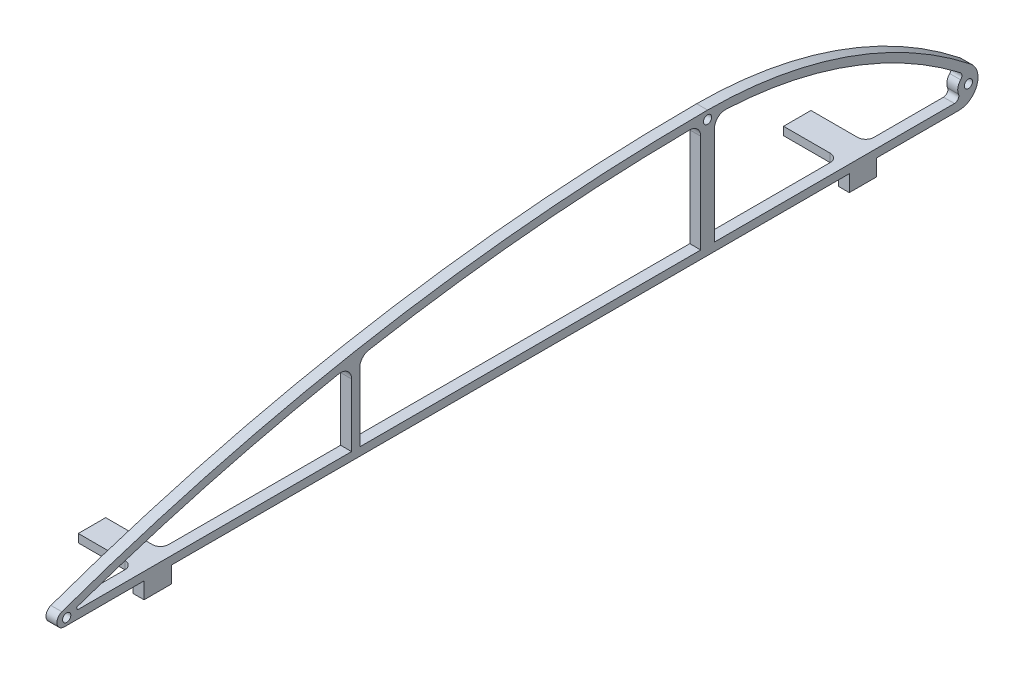
SolidWorks part; units mm, degrees
other "Marquage1"
sketch "Esquisse8" plane through (8, 0, -172.8424) normal (1, 0, 0) x (0, 0, -1)
other "Marquage2"
sketch "Esquisse10" plane through (-6, 20, -172.8424) normal (-0.8365, 0.2588, -0.483) x (-0.5, 0, 0.866)
other "Marquage3"
sketch "Esquisse11" plane through (0, 0, 0) normal (-0.0501, -0.1345, 0.9896) x (0.9942, 0.0873, 0.0622)
ref_plane "Plan de face" through (0, 0, 0) normal (0, 0, 1) x (1, 0, 0)
ref_plane "Plan de dessus" through (0, 0, 0) normal (0, 1, 0) x (1, 0, 0)
ref_plane "Plan de droite" through (0, 0, 0) normal (1, 0, 0) x (0, 0, -1)
sketch "Esquisse2" plane through (0, 0, 0) normal (1, 0, 0) x (0, 0, -1)
  line L0 (0, 0) -> (170.8732, 0)
  arc A1 (173.0499, 6.2408) -> (125, 23) centre (125, -54.2609) ccw
  arc A3 (170.8732, 0) -> (173.0499, 6.2408) centre (170.8732, 3.5) ccw
  arc A4 (125, 23) -> (0, 0) centre (125, -328.1739) ccw
  point P10 (180, 0)
  dimension "D1" = 180
  dimension "D2" = 3.5
  dimension "D3" = 23
  dimension "D4" = 55
extrude "Boss.-Extru.1" add sketch "Esquisse2" along normal blind 2
sketch "Esquisse4" plane through (2, 0, 0) normal (1, 0, 0) x (0, 0, -1)
  line L1 (0, 0) -> (8, 1.25) construction
  line L10 (174.369, 3.3283) -> (172.619, 3.3283) construction
  circle A6 centre (125, 21.5) radius 0.75
  circle A12 centre (172.619, 3.3283) radius 0.75
  arc A13 (170.8732, 0) -> (173.0499, 6.2408) centre (170.8732, 3.5) ccw construction
  circle A15 centre (8, 1.25) radius 0.75
  dimension "D1" = 1.5
  dimension "D2" = 1.5
  dimension "D7" = 1.5
  dimension "D3" = 1.5
  dimension "D4" = 8
  dimension "D5" = 1.25
  dimension "D6" = 1.75
extrude "Enlèv. mat.-Extru.2" cut sketch "Esquisse4" against normal through all
sketch "Esquisse9" plane through (0, 0, 0) normal (1, 0, 0) x (0, 0, -1)
  line L26 (126.25, 1.5) -> (171.941, 1.5)
  line L35 (8.4369, 1.5) -> (170.8732, 1.5)
  line L36 (9.9339, 1.5) -> (60, 1.5)
  line L40 (61.5, 1.5) -> (123.75, 1.5)
  line L42 (60, 1.5) -> (60, 15.4055)
  line L44 (61.5, 1.5) -> (61.5, 15.6859)
  line L45 (123.75, 21.4978) -> (123.75, 1.5)
  line L46 (126.25, 21.4978) -> (126.25, 1.5)
  arc A20 (60, 15.4055) -> (9.8076, 1.9814) centre (125, -328.1739) ccw
  circle A21 centre (125, 21.5) radius 0.75 construction
  circle A22 centre (8, 1.25) radius 0.75 construction
  arc A23 (173.0499, 6.2408) -> (125, 23) centre (125, -54.2609) ccw construction
  arc A25 (171.9926, 5.175) -> (171.941, 1.5) centre (172.619, 3.3283) ccw
  circle A26 centre (172.619, 3.3283) radius 0.75 construction
  arc A35 (170.8732, 1.5) -> (172.117, 5.0662) centre (170.8732, 3.5) ccw
  arc A39 (172.117, 5.0662) -> (125, 21.5) centre (125, -54.2609) ccw
  arc A40 (125, 21.5) -> (8.4369, 1.5) centre (125, -328.1739) ccw
  arc A42 (171.9926, 5.175) -> (126.25, 21.4978) centre (125, -54.2609) ccw
  arc A43 (123.75, 21.4978) -> (61.5, 15.6859) centre (125, -328.1739) ccw
  arc A54 (9.9339, 1.5) -> (9.8076, 1.9814) centre (8, 1.25) ccw
  dimension "D1" = 1.5
  dimension "D2" = 1.25
  dimension "D3" = 1.2
  dimension "D5" = 1.25
  dimension "D4" = 1.2
  dimension "D6" = 1.5
  dimension "D7" = 60
extrude "Enlèv. mat.-Extru.3" cut sketch "Esquisse9" along normal blind 4
fillet "Congé2" radius 1.35 1 edges at (1, 0, 0)
sketch "Esquisse12" plane through (0, 0, 0) normal (0, -1, 0) x (1, 0, 0)
  line L0 (0, -155.8732) -> (2, -155.8732)
  line L1 (0, -7.5659) -> (0, -170.8732) construction
  line L2 (2, -7.5659) -> (2, -170.8732) construction
  line L3 (2, -170.8732) -> (0, -170.8732) construction
  line L4 (0, -150.8732) -> (2, -150.8732)
  line L5 (0, -27.1127) -> (2, -27.1127)
  line L6 (0, -22.1127) -> (2, -22.1127)
  line L7 (0, -7.1127) -> (2, -7.1127) construction
  line M5 (2, -170.8732) -> (2, -7.5659)
  line M7 (0, -7.5659) -> (0, -170.8732)
  dimension "D1" = 15
  dimension "D2" = 5
  dimension "D3" = 15
  dimension "D4" = 5
extrude "Boss.-Extru.2" add sketch "Esquisse12" along normal blind 3 contours L4 L0 M7 M5 | L6 L5 M7 M5 region at (1, 0, -153.3732) region at (1, 0, -24.6127)
fillet "Congé3" radius 2 4 edges at (1, 21.4978, -126.25) (1, 21.4978, -123.75) (1, 15.4055, -60) (1, 15.6859, -61.5)
fillet "Congé4" radius 0.8 2 edges at (1, 1.5, -171.941) (1, 5.175, -171.9926)
sketch "Esquisse13" plane through (0, 0, 0) normal (-1, 0, 0) x (0, 0, 1)
  line L1 (-150.8732, -3) -> (-150.8732, 0) construction
  line L2 (-155.8732, 0) -> (-150.8732, 0)
  line L3 (-155.8732, 0) -> (-155.8732, 1.5)
  line L4 (-155.8732, 1.5) -> (-150.8732, 1.5)
  line L5 (-150.8732, 0) -> (-150.8732, 1.5)
  line L6 (-126.25, 1.5) -> (-170.0685, 1.5) construction
  line L7 (-22.1127, -3) -> (-22.1127, 0) construction
  line L8 (-27.1127, 0) -> (-22.1127, 0)
  line L9 (-27.1127, 0) -> (-27.1127, 1.5)
  line L10 (-27.1127, 1.5) -> (-22.1127, 1.5)
  line L11 (-22.1127, 0) -> (-22.1127, 1.5)
  line L12 (-9.9339, 1.5) -> (-60, 1.5) construction
extrude "Boss.-Extru.3" add sketch "Esquisse13" along normal blind 10
fillet "Congé5" radius 1.5 4 edges at (0, 0.75, -22.1127) (0, 0.75, -27.1127) (0, 0.75, -155.8732) (0, 0.75, -150.8732)
